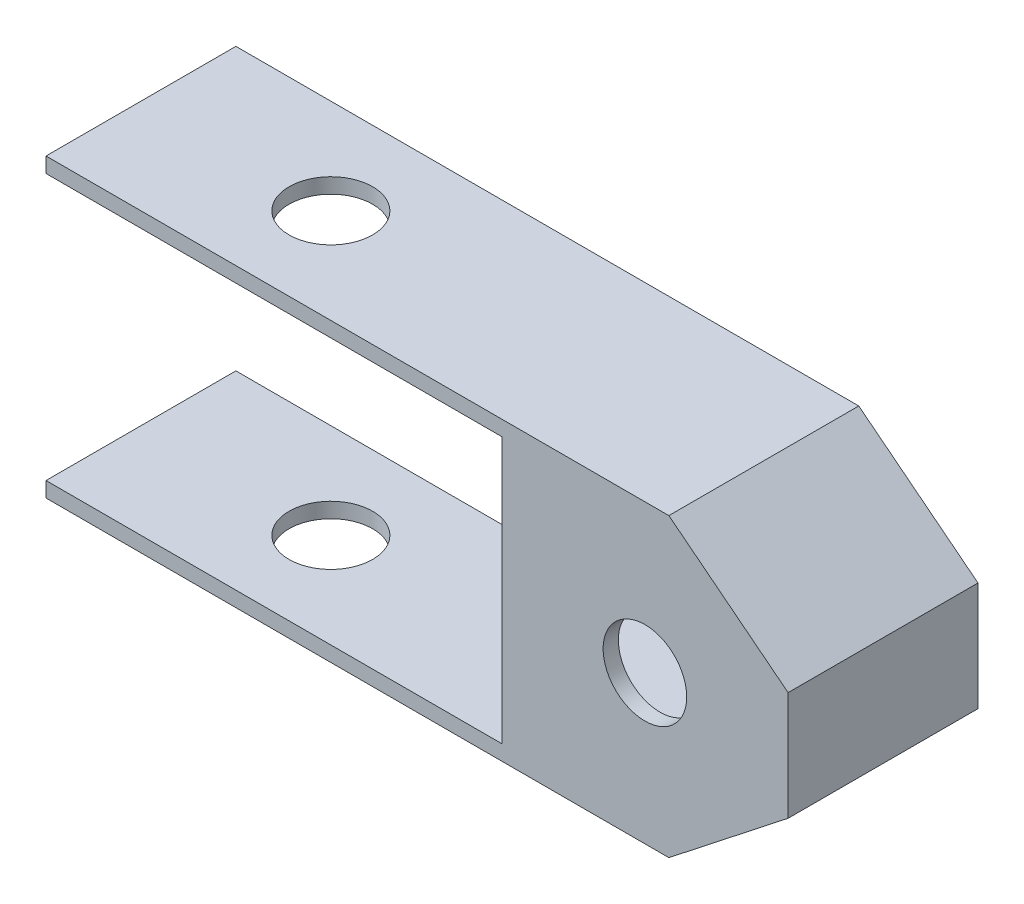
SolidWorks part; units mm, degrees
ref_plane "Plano frontal" through (0, 0, 0) normal (0, 0, 1) x (1, 0, 0)
ref_plane "Plano superior" through (0, 0, 0) normal (0, 1, 0) x (1, 0, 0)
ref_plane "Plano direito" through (0, 0, 0) normal (1, 0, 0) x (0, 0, -1)
sketch "Esboço1" plane through (0, 0, 0) normal (0, 0, 1) x (1, 0, 0)
  line L1 (-60, 0) -> (-60, 2)
  line L2 (0, 0) -> (2, 0)
  line L4 (2, 2) -> (-60, 2)
  line L5 (2, 2) -> (22, 2)
  line L6 (22, 2) -> (37.6969, -10.3347)
  line L7 (-60, 0) -> (-60, -35)
  line L9 (37.6969, -24.6653) -> (37.6969, -10.3347)
  line L10 (22, -37) -> (37.6969, -24.6653)
  line L11 (2, -37) -> (22, -37)
  line L12 (2, -37) -> (-60, -37)
  line L15 (-60, -35) -> (-60, -37)
  dimension "D1" = 60
  dimension "D2" = 2
  dimension "D3" = 2
  dimension "D4" = 2
  dimension "D5" = 20
  dimension "D6" = 141.84
  dimension "D7" = 35
extrude "Ressalto-extrusão2" add sketch "Esboço1" along normal blind 25 contours L7 L15 L12 L11 L10 L9 L6 L5 L4 L1 region at (-13.4866, -17.5, 0)
sketch "Esboço6" plane through (0, 0, 25) normal (0, 0, 1) x (1, 0, 0)
  line L0 (-60, 2) -> (-60, 0)
  line L1 (-60, 0) -> (0, 0)
  line L2 (0, 0) -> (0, -35)
  line L3 (0, -35) -> (-60, -35)
  line L4 (-60, 2) -> (-60, -37) construction
  line L5 (-60, -35) -> (-60, 0)
  line M1 (-60, 2) -> (-60, -37)
  dimension "D1" = 2
  dimension "D2" = 60
  dimension "D3" = 35
  dimension "D4" = 60
extrude "Corte-extrusão4" cut sketch "Esboço6" against normal blind 25 contours L3 L2 L1 M1 region at (-30, -17.5, 25)
sketch "Esboço7" plane through (0, 2, 0) normal (0, 1, 0) x (1, 0, 0)
  line L0 (-60, -12.5) -> (-35, -12.5)
  line L1 (-60, -25) -> (-60, 0) construction
  circle A0 centre (-35, -12.5) radius 5.5
  dimension "D2" = 11
  dimension "D1" = 25
extrude "Corte-extrusão5" cut sketch "Esboço7" against normal blind 67 contours A0 region at (-35, 2, 17.8444)
sketch "Esboço8" plane through (0, 0, 25) normal (0, 0, 1) x (1, 0, 0)
  line L0 (37.6969, -17.5) -> (0, -17.5)
  line L1 (37.6969, -24.6653) -> (37.6969, -10.3347) construction
  line L2 (0, 0) -> (0, -35) construction
  circle A0 centre (18.8485, -17.5) radius 5.5
  dimension "D1" = 11
shell "Casca3" thickness 2 removed face at (0, -17.5, 12.5)
extrude "Corte-extrusão7" cut sketch "Esboço8" against normal blind 67 contours L0 A0 | L0 A0 region at (18.8485, -19.8343, 25) region at (18.8485, -15.1657, 25)
